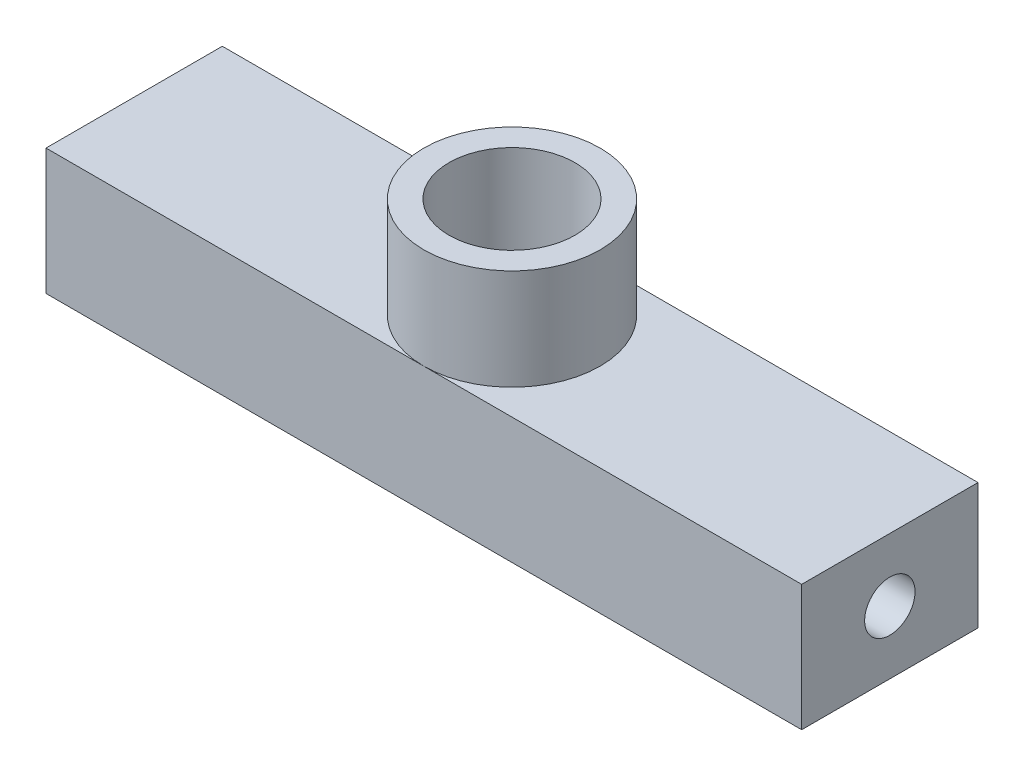
SolidWorks part; units mm, degrees
ref_plane "Front Plane" through (0, 0, 0) normal (0, 0, 1) x (1, 0, 0)
ref_plane "Top Plane" through (0, 0, 0) normal (0, 1, 0) x (1, 0, 0)
ref_plane "Right Plane" through (0, 0, 0) normal (1, 0, 0) x (0, 0, -1)
sketch "Sketch1" plane through (0, 0, 0) normal (0, 1, 0) x (1, 0, 0)
  line L1 (-15, 3.5) -> (15, 3.5)
  line L2 (-15, 3.5) -> (-15, -3.5)
  line L3 (-15, -3.5) -> (15, -3.5)
  line L4 (15, 3.5) -> (15, -3.5)
  line L5 (-15, 3.5) -> (15, -3.5) construction
  line L6 (-15, -3.5) -> (15, 3.5) construction
  point P0 (0, 0)
  dimension "D1" = 30
  dimension "D2" = 7
extrude "Boss-Extrude1" add sketch "Sketch1" along normal blind 5
sketch "Sketch2" plane through (0, 5, 0) normal (0, 1, 0) x (1, 0, 0)
  circle A0 centre (0, 0) radius 3.5
  circle A1 centre (0, 0) radius 2.5
  dimension "D1" = 7
  dimension "D2" = 5
extrude "Boss-Extrude2" add sketch "Sketch2" along normal blind 4
sketch "Sketch3" plane through (0, 0, 0) normal (0, -1, 0) x (1, 0, 0)
  circle A0 centre (0, 0) radius 1.75
  dimension "D1" = 3.5
extrude "Cut-Extrude1" cut sketch "Sketch3" against normal through all
sketch "Sketch4" plane through (0, 0, 0) normal (0, -1, 0) x (-1, 0, 0)
  circle A0 centre (0, 0) radius 2.5
  dimension "D1" = 5
extrude "Cut-Extrude3" cut sketch "Sketch4" against normal blind 4
sketch "Sketch5" plane through (15, 0, 0) normal (1, 0, 0) x (0, 0, -1)
  line L0 (3.5, 5) -> (3.5, 0) construction
  line L1 (-3.5, 5) -> (3.5, 5) construction
  circle A0 centre (0, 2.5) radius 1
  dimension "D1" = 2
  dimension "D2" = 3.5
  dimension "D3" = 2.5
extrude "Cut-Extrude4" cut sketch "Sketch5" against normal blind 10
sketch "Sketch6" plane through (-15, 0, 0) normal (-1, 0, 0) x (0, 0, 1)
  line L0 (-3.5, 5) -> (-3.5, 0) construction
  line L1 (-3.5, 5) -> (3.5, 5) construction
  circle A0 centre (0, 2.5) radius 1
  dimension "D1" = 2
  dimension "D2" = 3.5
  dimension "D3" = 2.5
extrude "Cut-Extrude5" cut sketch "Sketch6" against normal blind 10
